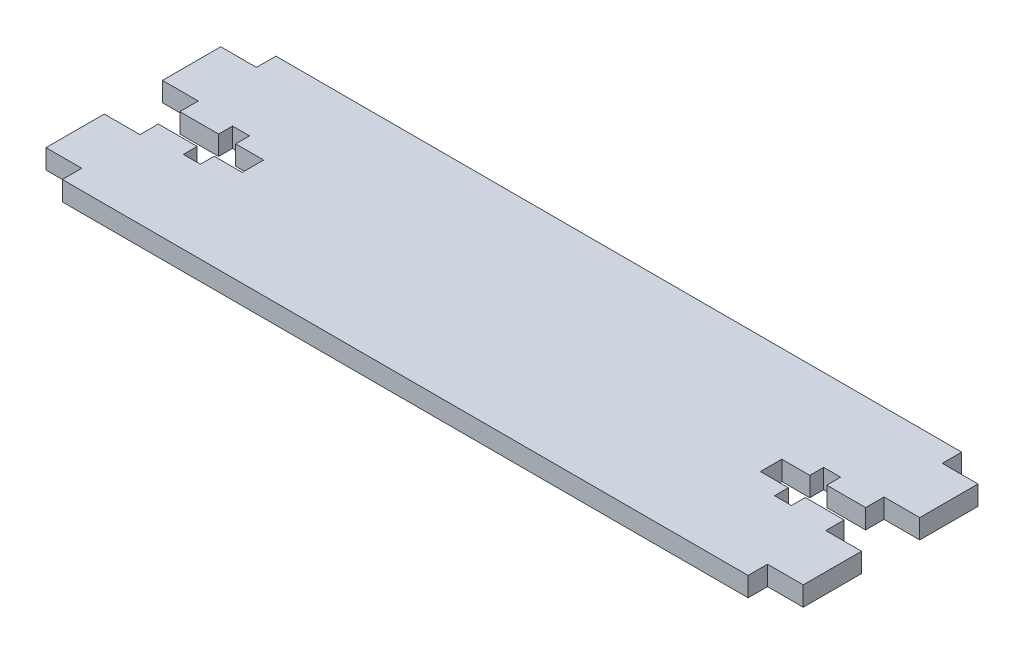
SolidWorks part; units mm, degrees
ref_plane "Front Plane" through (0, 0, 0) normal (0, 0, 1) x (1, 0, 0)
ref_plane "Top Plane" through (0, 0, 0) normal (0, 1, 0) x (1, 0, 0)
ref_plane "Right Plane" through (0, 0, 0) normal (1, 0, 0) x (0, 0, -1)
sketch "Sketch1" plane through (0, 0, 0) normal (0, 1, 0) x (1, 0, 0)
  line L0 (0, 17.4625) -> (0, -17.4625) construction
  line L1 (56.0705, -17.4625) -> (-56.0705, -17.4625)
  line L2 (-56.0705, -4.7625) -> (-56.0705, 4.7625)
  line L3 (56.0705, 17.4625) -> (-56.0705, 17.4625)
  line L4 (-56.0705, 14.2875) -> (-56.0705, 17.4625)
  line L5 (56.0705, -17.4625) -> (-56.0705, 17.4625) construction
  line L6 (56.0705, 17.4625) -> (-56.0705, -17.4625) construction
  line L7 (56.0705, 0) -> (-32.4683, 0) construction
  line L8 (-56.0705, 4.7625) -> (-61.9125, 4.7625)
  line L9 (-56.0705, -14.2875) -> (-56.0705, -17.4625)
  line L10 (-56.0705, 14.2875) -> (-61.9125, 14.2875)
  line L11 (-61.9125, 4.7625) -> (-61.9125, 14.2875)
  line L12 (-56.0705, -14.2875) -> (-61.9125, -14.2875)
  line L13 (-61.9125, -4.7625) -> (-61.9125, -14.2875)
  line L14 (-56.0705, -4.7625) -> (-61.9125, -4.7625)
  line L15 (56.0705, -4.7625) -> (61.9125, -4.7625)
  line L16 (61.9125, -4.7625) -> (61.9125, -14.2875)
  line L17 (56.0705, -14.2875) -> (61.9125, -14.2875)
  line L18 (61.9125, 4.7625) -> (61.9125, 14.2875)
  line L19 (56.0705, 14.2875) -> (61.9125, 14.2875)
  line L20 (56.0705, -14.2875) -> (56.0705, -17.4625)
  line L21 (56.0705, 4.7625) -> (61.9125, 4.7625)
  line L22 (56.0705, 14.2875) -> (56.0705, 17.4625)
  line L23 (56.0705, -4.7625) -> (56.0705, 4.7625)
  point P0 (0, 0)
  point P10 (-58.9915, 0)
  point P14 (-56.0705, 0)
  point P19 (58.9915, 0)
  dimension "D1" = 9.525
  dimension "D2" = 5.842
  dimension "D3" = 112.141
  dimension "D4" = 34.925
  dimension "D5" = 9.525
extrude "Boss-Extrude1" add sketch "Sketch1" along normal blind 3.175
sketch "Sketch2" plane through (0, 3.175, 0) normal (0, 1, 0) x (1, 0, 0)
  line L0 (-56.0705, 0) -> (56.0705, 0) construction
  line L1 (-56.0705, 4.7625) -> (-56.0705, -4.7625) construction
  line L2 (56.0705, -4.7625) -> (56.0705, 4.7625) construction
  line L3 (-49.7205, 1.7526) -> (-49.7205, 4.0187)
  line L4 (-49.7205, -1.7526) -> (-56.0705, -1.7526)
  line L5 (0, 17.4625) -> (0, -17.4625) construction
  line L6 (-49.7205, 1.7526) -> (-56.0705, 1.7526)
  line L7 (-56.0705, -1.7526) -> (-56.0705, 1.7526)
  line L8 (-49.7205, -1.7526) -> (-56.0705, 1.7526) construction
  line L9 (-49.7205, 1.7526) -> (-56.0705, -1.7526) construction
  line L10 (-46.9424, -4.0188) -> (-49.7205, -4.0188)
  line L11 (-46.9424, -4.0188) -> (-46.9424, -1.7526)
  line L12 (-46.9424, 4.0187) -> (-49.7205, 4.0187)
  line L13 (-49.7205, -4.0188) -> (-49.7205, -1.7526)
  line L14 (-46.9424, -4.0188) -> (-49.7205, 4.0187) construction
  line L15 (-46.9424, 4.0187) -> (-49.7205, -4.0188) construction
  line L16 (-42.3625, -1.7526) -> (-46.9424, -1.7526)
  line L17 (-42.3625, -1.7526) -> (-42.3625, 1.7526)
  line L18 (-42.3625, 1.7526) -> (-46.9424, 1.7526)
  line L19 (56.0705, 17.4625) -> (-56.0705, 17.4625) construction
  line L20 (-42.3625, -1.7526) -> (-46.9424, 1.7526) construction
  line L21 (-42.3625, 1.7526) -> (-46.9424, -1.7526) construction
  line L22 (-46.9424, 1.7526) -> (-46.9424, 4.0187)
  line L23 (-56.0705, -17.4625) -> (56.0705, -17.4625) construction
  line L24 (42.3625, 1.7526) -> (46.9424, -1.7526) construction
  line L25 (42.3625, -1.7526) -> (46.9424, 1.7526) construction
  line L26 (46.9424, 4.0187) -> (49.7205, -4.0188) construction
  line L27 (46.9424, -4.0188) -> (49.7205, 4.0187) construction
  line L28 (49.7205, 1.7526) -> (56.0705, -1.7526) construction
  line L29 (49.7205, -1.7526) -> (56.0705, 1.7526) construction
  line L30 (46.9424, 1.7526) -> (46.9424, 4.0187)
  line L31 (42.3625, 1.7526) -> (46.9424, 1.7526)
  line L32 (42.3625, -1.7526) -> (42.3625, 1.7526)
  line L33 (42.3625, -1.7526) -> (46.9424, -1.7526)
  line L34 (49.7205, -4.0188) -> (49.7205, -1.7526)
  line L35 (46.9424, 4.0187) -> (49.7205, 4.0187)
  line L36 (46.9424, -4.0188) -> (46.9424, -1.7526)
  line L37 (46.9424, -4.0188) -> (49.7205, -4.0188)
  line L38 (56.0705, -1.7526) -> (56.0705, 1.7526)
  line L39 (49.7205, 1.7526) -> (56.0705, 1.7526)
  line L40 (49.7205, -1.7526) -> (56.0705, -1.7526)
  line L41 (49.7205, 1.7526) -> (49.7205, 4.0187)
  point P6 (-52.8955, 0)
  point P11 (-48.3314, 0)
  point P16 (-44.6524, 0)
  point P39 (44.6524, 0)
  point P40 (48.3314, 0)
  point P41 (52.8955, 0)
  dimension "D1" = 3.5052
  dimension "D2" = 3.5052
  dimension "D3" = 8.0375
  dimension "D4" = 6.35
  dimension "D5" = 4.5799
  dimension "D6" = 2.7781
extrude "Cut-Extrude1" cut sketch "Sketch2" against normal through all
